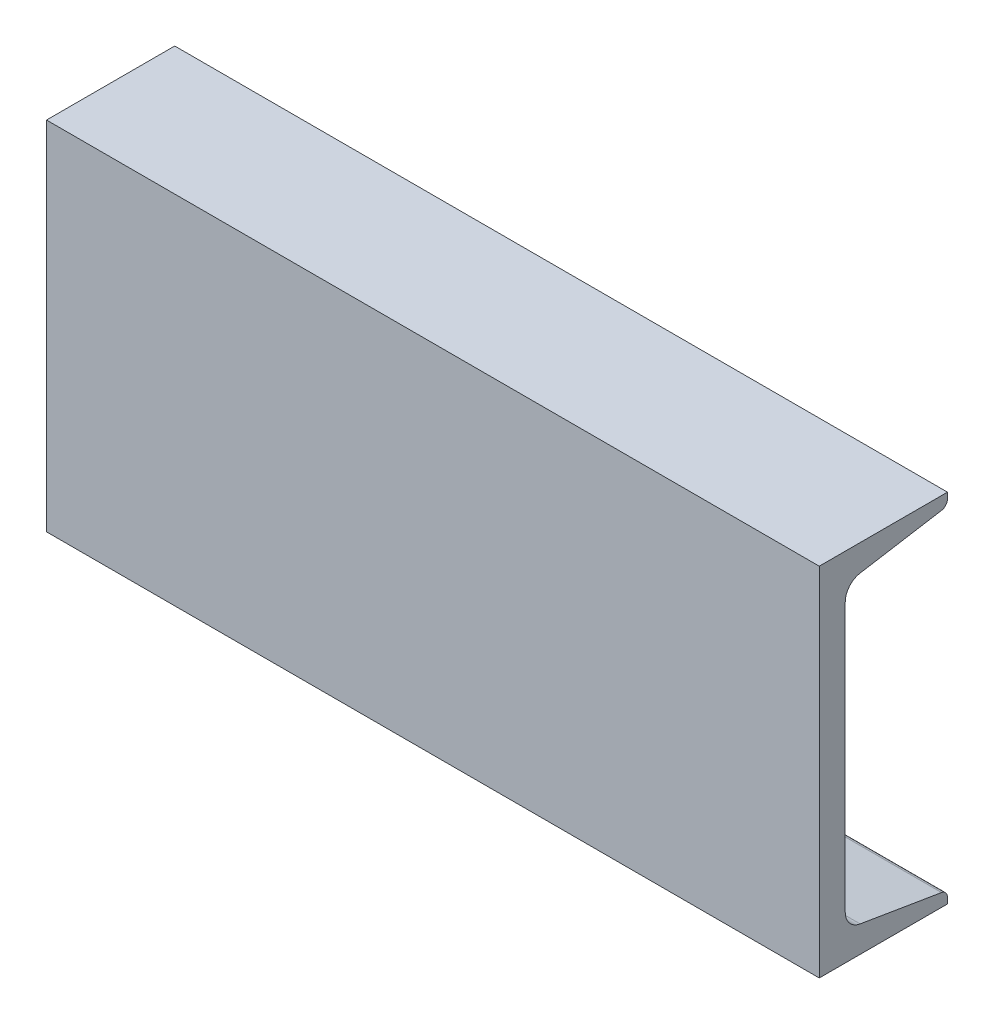
SolidWorks part; units mm, degrees
ref_plane "Front Plane" through (0, 0, 0) normal (0, 0, 1) x (1, 0, 0)
ref_plane "Top Plane" through (0, 0, 0) normal (0, 1, 0) x (1, 0, 0)
ref_plane "Right Plane" through (0, 0, 0) normal (1, 0, 0) x (0, 0, -1)
sketch "Sketch1" plane through (0, 0, 0) normal (1, 0, 0) x (0, 0, -1)
  line L0 (-27.3939, -76.2) -> (-27.3939, 76.2)
  line L1 (-27.3939, 76.2) -> (27.3939, 76.2)
  line L2 (-27.3939, -76.2) -> (27.3939, -76.2)
  line L3 (4.3561, -67.4878) -> (-21.0439, -67.4878) construction
  line L4 (-16.2941, 57.3918) -> (-16.2941, -57.3918)
  line L5 (27.3939, 76.2) -> (27.3939, 73.7107)
  line L6 (27.3939, -76.2) -> (27.3939, -73.7107)
  line L7 (-9.9269, 64.9081) -> (24.847, 70.7042)
  line L8 (-9.9269, -64.9081) -> (24.847, -70.7042)
  arc A0 (-16.2941, -57.3918) -> (-9.9269, -64.9081) centre (-8.6741, -57.3918) ccw
  arc A1 (-16.2941, 57.3918) -> (-9.9269, 64.9081) centre (-8.6741, 57.3918) cw
  arc A2 (27.3939, 73.7107) -> (24.847, 70.7042) centre (24.3459, 73.7107) cw
  arc A3 (27.3939, -73.7107) -> (24.847, -70.7042) centre (24.3459, -73.7107) ccw
extrude "Boss-Extrude1" add sketch "Sketch1" along normal mid plane 330.2
